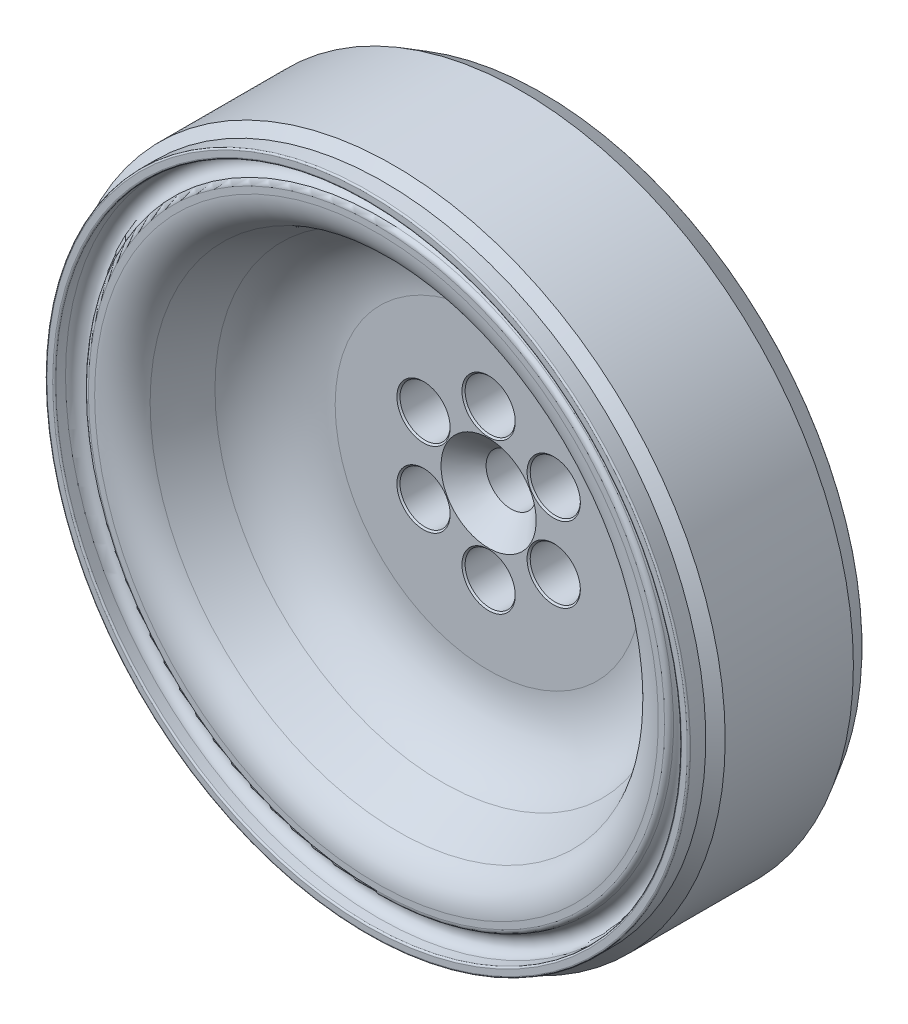
SolidWorks part; units mm, degrees
material "4340 H/T"
ref_plane "Front Plane" through (0, 0, 0) normal (0, 0, 1) x (1, 0, 0)
ref_plane "Top Plane" through (0, 0, 0) normal (0, 1, 0) x (1, 0, 0)
ref_plane "Right Plane" through (0, 0, 0) normal (1, 0, 0) x (0, 0, -1)
sketch "Sketch1" plane through (0, 0, 0) normal (1, 0, 0) x (0, 0, -1)
  line L0 (0, 4.75) -> (0, 18.98)
  line L1 (0, 18.98) -> (-1, 19.98)
  line L2 (-1, 19.98) -> (-7.7, 19.98)
  line L3 (-8.5, 20.78) -> (-8.5, 28)
  line L4 (-8.5, 51) -> (-11.8342, 52.925)
  line L5 (-11.8342, 52.925) -> (-32.3, 52.925)
  line L6 (-32.3, 52.925) -> (-33.85, 51.375)
  line L7 (-33.85, 51.375) -> (-36.3, 51.375)
  line L8 (-36.55, 51.125) -> (-36.55, 50.2)
  line L9 (-36.3, 49.95) -> (-34.75, 49.95)
  line L10 (-35.05, 46.0027) -> (-35.05, 45)
  line L11 (-31.6168, 39.5768) -> (-24.5886, 36.2504)
  line L12 (-17.15, 24.5) -> (-17.15, 7.6)
  line L13 (-17.15, 7.6) -> (-13.55, 4)
  line L14 (-8.5, 37) -> (-8.8, 37)
  line L15 (-8.8, 37) -> (-8.8, 28)
  line L16 (-13.55, 4) -> (-0.75, 4)
  line L17 (-0.75, 4) -> (0, 4.75)
  line L18 (0, 0) -> (-36.8, 0) construction
  line L19 (-8.8, 28) -> (-8.5, 28)
  line L20 (-8.5, 37) -> (-8.5, 51)
  arc A0 (-34.75, 49.95) -> (-34.4167, 46.7851) centre (-34.75, 48.35) cw
  arc A1 (-35.05, 45) -> (-31.6168, 39.5768) centre (-29.05, 45) ccw
  arc A2 (-24.5886, 36.2504) -> (-17.15, 24.5) centre (-30.15, 24.5) cw
  arc A3 (-35.05, 46.0027) -> (-34.4167, 46.7851) centre (-34.25, 46.0027) cw
  arc A4 (-36.55, 50.2) -> (-36.3, 49.95) centre (-36.3, 50.2) ccw
  arc A5 (-36.3, 51.375) -> (-36.55, 51.125) centre (-36.3, 51.125) ccw
  arc A6 (-7.7, 19.98) -> (-8.5, 20.78) centre (-7.7, 20.78) cw
  dimension "D22" = 6
  dimension "D23" = 13
  dimension "D26" = 1.6
  dimension "D20" = 3.4
  dimension "D19" = 0.8
  dimension "D28" = 0.25
  dimension "D29" = 0.25
  dimension "D30" = 74
  dimension "D33" = 0.8
  dimension "D1" = 28.05
  dimension "D2" = 8.5
  dimension "D3" = 39.96
  dimension "D4" = 45
  dimension "D5" = 1
  dimension "D6" = 105.85
  dimension "D7" = 102
  dimension "D8" = 30
  dimension "D9" = 102.75
  dimension "D10" = 2.7
  dimension "D11" = 45
  dimension "D12" = 8
  dimension "D13" = 9.5
  dimension "D14" = 45
  dimension "D15" = 15.2
  dimension "D16" = 45
  dimension "D17" = 19.4
  dimension "D18" = 99.9
  dimension "D21" = 1.5
  dimension "D24" = 49
  dimension "D25" = 90
  dimension "D27" = 96.7
  dimension "D31" = 56
  dimension "D32" = 0.3
revolve "Revolve1" add sketch "Sketch1" angle 360 about L18
cosmetic thread "Cosmetic Thread1" parameters "D2"=103.5
sketch "Sketch2" plane through (0, 0, 0) normal (0, 0, -1) x (-1, 0, 0)
  line L0 (0, 0) -> (0, 33.1148) construction
  point P3 (0, 12)
  dimension "D1" = 12
hole_wizard "M8.0 (8) Diameter Hole1" positions "3DSketch1" profile "Sketch3" hole size "M8.0" standard "Ansi Metric" end condition up to next
sketch3d "3DSketch1"
  point P0 (0, 12, 0)
sketch "Sketch3" plane through (0, 12, 0) normal (1, 0, 0) x (0, 1, 0)
  line L0 (0, 0) -> (0, 17.15)
  line L1 (0, 17.15) -> (4.25, 17.15)
  line L2 (4, 16.9) -> (4, 0.5)
  line L3 (4, 0.5) -> (4.5, 0)
  line L5 (4.5, 0) -> (0, 0)
  line L6 (-4, 0.5) -> (-4.5, 0) construction
  line L7 (4.25, 17.15) -> (4, 16.9)
  line L8 (-4.25, 17.15) -> (-4, 16.9) construction
  line L11 (0, -6.35) -> (0, 107.95) construction
  dimension "Thru Hole Dia." = 8
  dimension "Thru Hole Depth" = 17.15
  dimension "Near C'Sink Dia." = 9
  dimension "Near C'Sink Angle" = 90
  dimension "Far C'Sink Dia." = 8.5
  dimension "Far C'Sink Angle" = 90
ref_axis "Axis1" through (0, 0, 0.75) along (0, 0, 1)
pattern_circular "CirPattern1" count 6 over 360 about axis through (0, 0, 0.75) along (0, 0, 1) of "M8.0 (8) Diameter Hole1"
sketch "Sketch4" plane through (0, 0, 8.5) normal (0, 0, -1) x (-1, 0, 0)
  line L0 (0, 0) -> (0, 33.1148) construction
  point P0 (0, 45)
  dimension "D1" = 45
hole_wizard "M8.0 (8) Diameter Hole2" positions "3DSketch2" profile "Sketch5" hole size "M8.0" standard "Ansi Metric"
sketch3d "3DSketch2"
  point P0 (0, 45, 8.5)
sketch "Sketch5" plane through (0, 45, 8.5) normal (1, 0, 0) x (0, 1, 0)
  line L0 (0, 0) -> (0, 14.8034)
  line L1 (0, 14.8034) -> (4, 12.4)
  line L2 (4, 12.4) -> (4, 0.5)
  line L3 (4, 0.5) -> (4.5, 0)
  line L5 (4.5, 0) -> (0, 0)
  line L6 (-4, 0.5) -> (-4.5, 0) construction
  line L10 (0, 14.8034) -> (-4, 12.4) construction
  line L11 (0, -6.35) -> (0, 107.95) construction
  dimension "Hole Dia." = 8
  dimension "Hole Depth" = 12.4
  dimension "Near C'Sink Dia." = 9
  dimension "Near C'Sink Angle" = 90
  dimension "Drill Angle" = 118
pattern_circular "CirPattern2" count 2 over 360 about axis through (0, 0, 0.75) along (0, 0, 1) of "M8.0 (8) Diameter Hole2"
fillet "Fillet1" radius 0.25 1 edges at (-51, 0, 8.5)
